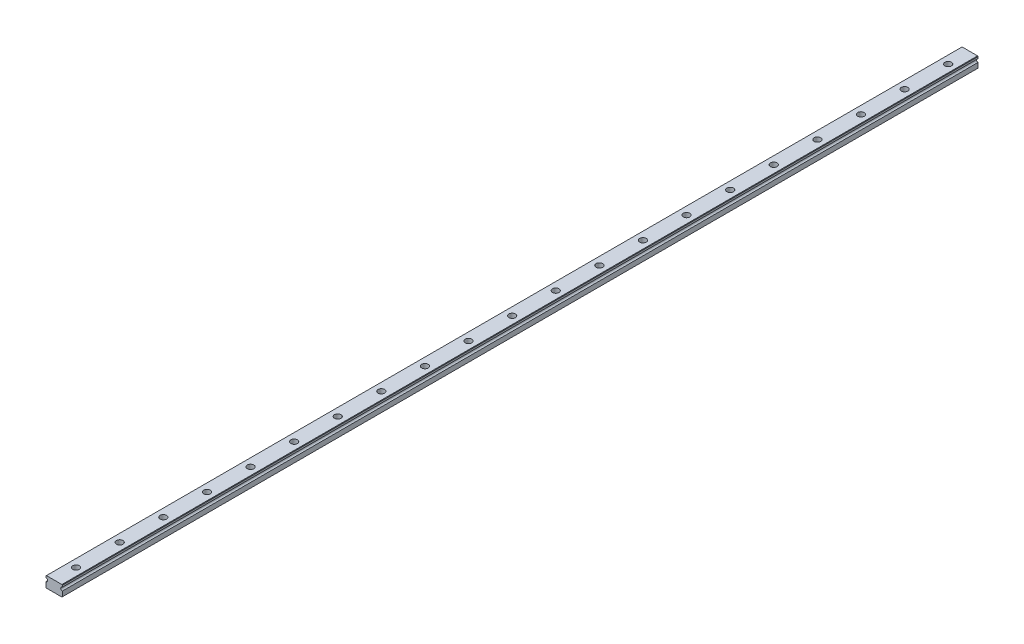
SolidWorks part; units mm, degrees
ref_plane "前视基准面" through (0, 0, 0) normal (0, 0, 1) x (1, 0, 0)
ref_plane "上视基准面" through (0, 0, 0) normal (0, 1, 0) x (1, 0, 0)
ref_plane "右视基准面" through (0, 0, 0) normal (1, 0, 0) x (0, 0, -1)
other "Configuration Table"
sketch "草图1" plane through (0, 0, 0) normal (0, 0, 1) x (1, 0, 0)
  line L0 (-7.6432, 0.2342) -> (-7.6432, -4.3658)
  line L1 (-7.6432, -4.3658) -> (-7.2432, -4.7658)
  line L2 (-7.2432, -4.7658) -> (6.9568, -4.7658)
  line L3 (6.9568, -4.7658) -> (7.3568, -4.3658)
  line L4 (7.3568, -4.3658) -> (7.3568, 0.2342)
  line L5 (7.3568, 3.2342) -> (7.3568, 4.8342)
  line L6 (7.3568, 4.8342) -> (6.9568, 5.2342)
  line L7 (6.9568, 5.2342) -> (-7.2432, 5.2342)
  line L8 (-7.2432, 5.2342) -> (-7.6432, 4.8342)
  line L9 (-7.6432, 4.8342) -> (-7.6432, 3.2342)
  arc A0 (5.8568, 1.7342) -> (7.3568, 0.2342) centre (7.3568, 1.7342) ccw
  arc A1 (7.3568, 3.2342) -> (5.8568, 1.7342) centre (7.3568, 1.7342) ccw
  arc A2 (-7.6432, 0.2342) -> (-7.6432, 3.2342) centre (-7.6432, 1.7342) ccw
extrude "凸台-拉伸1" add sketch "草图1" along normal blind 1000
sketch "草图2" plane through (0, 5.2342, 0) normal (0, 1, 0) x (1, 0, 0)
  line L0 (6.9568, 0) -> (-7.2432, 0) construction
  circle A0 centre (0, -20) radius 1.5
  dimension "D1" = 3
  dimension "D2" = 20
extrude "切除-拉伸1" cut sketch "草图2" against normal blind 20
sketch "草图3" plane through (0, 5.2342, 0) normal (0, 1, 0) x (1, 0, 0)
  circle A0 centre (0, -20) radius 3
  dimension "D1" = 6
extrude "切除-拉伸2" cut sketch "草图3" against normal blind 4.5
sketch "草图4" plane through (0, 5.2342, 0) normal (0, 1, 0) x (1, 0, 0)
  line L0 (0, 0) -> (0, -1341.5051) construction
pattern_linear "阵列(线性)1" count 25 spacing 40 along (0, 0, 1) of "切除-拉伸2", "切除-拉伸1"
sketch "草图5" plane through (0, 0, 1000) normal (0, 0, 1) x (1, 0, 0)
  line L10 (-7.6432, 0.2342) -> (-7.6432, -4.3658)
  line L11 (-7.6432, -4.3658) -> (-7.2432, -4.7658)
  line L12 (-7.2432, -4.7658) -> (6.9568, -4.7658)
  line L13 (6.9568, -4.7658) -> (7.3568, -4.3658)
  line L14 (7.3568, -4.3658) -> (7.3568, 0.2342)
  line L15 (7.3568, 3.2342) -> (7.3568, 4.8342)
  line L16 (7.3568, 4.8342) -> (6.9568, 5.2342)
  line L17 (6.9568, 5.2342) -> (-7.2432, 5.2342)
  line L18 (-7.2432, 5.2342) -> (-7.6432, 4.8342)
  line L19 (-7.6432, 4.8342) -> (-7.6432, 3.2342)
  line L20 (-7.6432, 0.2342) -> (-7.6432, -4.3658)
  line L21 (-7.6432, -4.3658) -> (-7.2432, -4.7658)
  line L22 (-7.2432, -4.7658) -> (6.9568, -4.7658)
  line L23 (6.9568, -4.7658) -> (7.3568, -4.3658)
  line L24 (7.3568, -4.3658) -> (7.3568, 0.2342)
  line L25 (7.3568, 3.2342) -> (7.3568, 4.8342)
  line L26 (7.3568, 4.8342) -> (6.9568, 5.2342)
  line L27 (6.9568, 5.2342) -> (-7.2432, 5.2342)
  line L28 (-7.2432, 5.2342) -> (-7.6432, 4.8342)
  line L29 (-7.6432, 4.8342) -> (-7.6432, 3.2342)
  arc A2 (-7.6432, 0.2342) -> (-7.6432, 3.2342) centre (-7.6432, 1.7342) ccw
  arc A3 (7.3568, 3.2342) -> (7.3568, 0.2342) centre (7.3568, 1.7342) ccw
  arc A4 (-7.6432, 0.2342) -> (-7.6432, 3.2342) centre (-7.6432, 1.7342) ccw
  arc A5 (7.3568, 3.2342) -> (7.3568, 0.2342) centre (7.3568, 1.7342) ccw
  dimension "D1" = 0
sketch "草图6" plane through (0, 0, 0) normal (0, 0, -1) x (-1, 0, 0)
  line L10 (7.6432, 3.2342) -> (7.6432, 4.8342)
  line L11 (7.6432, 4.8342) -> (7.2432, 5.2342)
  line L12 (7.2432, 5.2342) -> (-6.9568, 5.2342)
  line L13 (-6.9568, 5.2342) -> (-7.3568, 4.8342)
  line L14 (-7.3568, 4.8342) -> (-7.3568, 3.2342)
  line L15 (-7.3568, 0.2342) -> (-7.3568, -4.3658)
  line L16 (-7.3568, -4.3658) -> (-6.9568, -4.7658)
  line L17 (-6.9568, -4.7658) -> (7.2432, -4.7658)
  line L18 (7.2432, -4.7658) -> (7.6432, -4.3658)
  line L19 (7.6432, -4.3658) -> (7.6432, 0.2342)
  line L20 (7.6432, 3.2342) -> (7.6432, 4.8342)
  line L21 (7.6432, 4.8342) -> (7.2432, 5.2342)
  line L22 (7.2432, 5.2342) -> (-6.9568, 5.2342)
  line L23 (-6.9568, 5.2342) -> (-7.3568, 4.8342)
  line L24 (-7.3568, 4.8342) -> (-7.3568, 3.2342)
  line L25 (-7.3568, 0.2342) -> (-7.3568, -4.3658)
  line L26 (-7.3568, -4.3658) -> (-6.9568, -4.7658)
  line L27 (-6.9568, -4.7658) -> (7.2432, -4.7658)
  line L28 (7.2432, -4.7658) -> (7.6432, -4.3658)
  line L29 (7.6432, -4.3658) -> (7.6432, 0.2342)
  arc A2 (7.6432, 3.2342) -> (7.6432, 0.2342) centre (7.6432, 1.7342) ccw
  arc A3 (-7.3568, 0.2342) -> (-7.3568, 3.2342) centre (-7.3568, 1.7342) ccw
  arc A4 (7.6432, 3.2342) -> (7.6432, 0.2342) centre (7.6432, 1.7342) ccw
  arc A5 (-7.3568, 0.2342) -> (-7.3568, 3.2342) centre (-7.3568, 1.7342) ccw
  dimension "D1" = 0
extrude "切除-拉伸4" cut sketch "草图6" against normal blind 80
sketch "草图7" plane through (0, 0, 80) normal (0, 0, -1) x (-1, 0, 0)
  line L10 (7.6432, 3.2342) -> (7.6432, 4.8342)
  line L11 (7.6432, 4.8342) -> (7.2432, 5.2342)
  line L12 (7.2432, 5.2342) -> (-6.9568, 5.2342)
  line L13 (-6.9568, 5.2342) -> (-7.3568, 4.8342)
  line L14 (-7.3568, 4.8342) -> (-7.3568, 3.2342)
  line L15 (-7.3568, 0.2342) -> (-7.3568, -4.3658)
  line L16 (-7.3568, -4.3658) -> (-6.9568, -4.7658)
  line L17 (-6.9568, -4.7658) -> (7.2432, -4.7658)
  line L18 (7.2432, -4.7658) -> (7.6432, -4.3658)
  line L19 (7.6432, -4.3658) -> (7.6432, 0.2342)
  line L20 (7.6432, 3.2342) -> (7.6432, 4.8342)
  line L21 (7.6432, 4.8342) -> (7.2432, 5.2342)
  line L22 (7.2432, 5.2342) -> (-6.9568, 5.2342)
  line L23 (-6.9568, 5.2342) -> (-7.3568, 4.8342)
  line L24 (-7.3568, 4.8342) -> (-7.3568, 3.2342)
  line L25 (-7.3568, 0.2342) -> (-7.3568, -4.3658)
  line L26 (-7.3568, -4.3658) -> (-6.9568, -4.7658)
  line L27 (-6.9568, -4.7658) -> (7.2432, -4.7658)
  line L28 (7.2432, -4.7658) -> (7.6432, -4.3658)
  line L29 (7.6432, -4.3658) -> (7.6432, 0.2342)
  arc A2 (7.6432, 3.2342) -> (7.6432, 0.2342) centre (7.6432, 1.7342) ccw
  arc A3 (-7.3568, 0.2342) -> (-7.3568, 3.2342) centre (-7.3568, 1.7342) ccw
  arc A4 (7.6432, 3.2342) -> (7.6432, 0.2342) centre (7.6432, 1.7342) ccw
  arc A5 (-7.3568, 0.2342) -> (-7.3568, 3.2342) centre (-7.3568, 1.7342) ccw
  dimension "D1" = 0
extrude "切除-拉伸5" cut sketch "草图7" against normal blind 80
sketch "草图8" plane through (0, 0, 160) normal (0, 0, -1) x (-1, 0, 0)
  line L10 (7.6432, 3.2342) -> (7.6432, 4.8342)
  line L11 (7.6432, 4.8342) -> (7.2432, 5.2342)
  line L12 (7.2432, 5.2342) -> (-6.9568, 5.2342)
  line L13 (-6.9568, 5.2342) -> (-7.3568, 4.8342)
  line L14 (-7.3568, 4.8342) -> (-7.3568, 3.2342)
  line L15 (-7.3568, 0.2342) -> (-7.3568, -4.3658)
  line L16 (-7.3568, -4.3658) -> (-6.9568, -4.7658)
  line L17 (-6.9568, -4.7658) -> (7.2432, -4.7658)
  line L18 (7.2432, -4.7658) -> (7.6432, -4.3658)
  line L19 (7.6432, -4.3658) -> (7.6432, 0.2342)
  line L20 (7.6432, 3.2342) -> (7.6432, 4.8342)
  line L21 (7.6432, 4.8342) -> (7.2432, 5.2342)
  line L22 (7.2432, 5.2342) -> (-6.9568, 5.2342)
  line L23 (-6.9568, 5.2342) -> (-7.3568, 4.8342)
  line L24 (-7.3568, 4.8342) -> (-7.3568, 3.2342)
  line L25 (-7.3568, 0.2342) -> (-7.3568, -4.3658)
  line L26 (-7.3568, -4.3658) -> (-6.9568, -4.7658)
  line L27 (-6.9568, -4.7658) -> (7.2432, -4.7658)
  line L28 (7.2432, -4.7658) -> (7.6432, -4.3658)
  line L29 (7.6432, -4.3658) -> (7.6432, 0.2342)
  arc A2 (7.6432, 3.2342) -> (7.6432, 0.2342) centre (7.6432, 1.7342) ccw
  arc A3 (-7.3568, 0.2342) -> (-7.3568, 3.2342) centre (-7.3568, 1.7342) ccw
  arc A4 (7.6432, 3.2342) -> (7.6432, 0.2342) centre (7.6432, 1.7342) ccw
  arc A5 (-7.3568, 0.2342) -> (-7.3568, 3.2342) centre (-7.3568, 1.7342) ccw
  dimension "D1" = 0
extrude "切除-拉伸6" [suppressed] cut sketch "草图8" against normal blind 20
sketch "草图9" plane through (0, 0, 1000) normal (0, 0, 1) x (1, 0, 0)
  line L10 (-7.6432, 0.2342) -> (-7.6432, -4.3658)
  line L11 (-7.6432, -4.3658) -> (-7.2432, -4.7658)
  line L12 (-7.2432, -4.7658) -> (6.9568, -4.7658)
  line L13 (6.9568, -4.7658) -> (7.3568, -4.3658)
  line L14 (7.3568, -4.3658) -> (7.3568, 0.2342)
  line L15 (7.3568, 3.2342) -> (7.3568, 4.8342)
  line L16 (7.3568, 4.8342) -> (6.9568, 5.2342)
  line L17 (6.9568, 5.2342) -> (-7.2432, 5.2342)
  line L18 (-7.2432, 5.2342) -> (-7.6432, 4.8342)
  line L19 (-7.6432, 4.8342) -> (-7.6432, 3.2342)
  line L20 (-7.6432, 0.2342) -> (-7.6432, -4.3658)
  line L21 (-7.6432, -4.3658) -> (-7.2432, -4.7658)
  line L22 (-7.2432, -4.7658) -> (6.9568, -4.7658)
  line L23 (6.9568, -4.7658) -> (7.3568, -4.3658)
  line L24 (7.3568, -4.3658) -> (7.3568, 0.2342)
  line L25 (7.3568, 3.2342) -> (7.3568, 4.8342)
  line L26 (7.3568, 4.8342) -> (6.9568, 5.2342)
  line L27 (6.9568, 5.2342) -> (-7.2432, 5.2342)
  line L28 (-7.2432, 5.2342) -> (-7.6432, 4.8342)
  line L29 (-7.6432, 4.8342) -> (-7.6432, 3.2342)
  arc A2 (-7.6432, 0.2342) -> (-7.6432, 3.2342) centre (-7.6432, 1.7342) ccw
  arc A3 (7.3568, 3.2342) -> (7.3568, 0.2342) centre (7.3568, 1.7342) ccw
  arc A4 (-7.6432, 0.2342) -> (-7.6432, 3.2342) centre (-7.6432, 1.7342) ccw
  arc A5 (7.3568, 3.2342) -> (7.3568, 0.2342) centre (7.3568, 1.7342) ccw
  dimension "D1" = 0
extrude "切除-拉伸7" [suppressed] cut sketch "草图9" against normal blind 360
